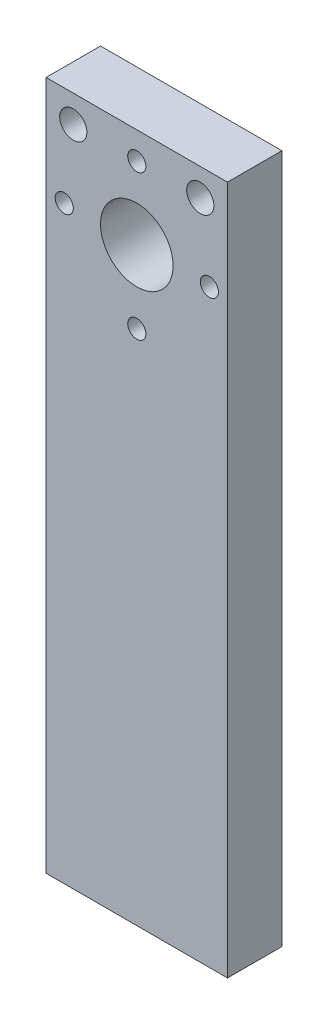
SolidWorks part; units mm, degrees
ref_plane "Plan de face" through (0, 0, 0) normal (0, 0, 1) x (1, 0, 0)
ref_plane "Plan de dessus" through (0, 0, 0) normal (0, 1, 0) x (1, 0, 0)
ref_plane "Plan de droite" through (0, 0, 0) normal (1, 0, 0) x (0, 0, -1)
sketch "Esquisse1" plane through (0, 0, 0) normal (0, 0, 1) x (1, 0, 0)
  line L1 (-10, 38) -> (10, 38)
  line L2 (-10, 38) -> (-10, -38)
  line L3 (-10, -38) -> (10, -38)
  line L4 (10, 38) -> (10, -38)
  dimension "D1" = 76
  dimension "D2" = 20
  dimension "D3" = 10
  dimension "D4" = 38
extrude "Boss.-Extru.1" add sketch "Esquisse1" along normal blind 6
sketch "Esquisse2" plane through (0, 0, 6) normal (0, 0, 1) x (1, 0, 0)
  line L0 (10, 38) -> (-10, 38) construction
  line L1 (45.7904, 0) -> (-37.4617, 0) construction
  line L2 (-19.8072, 35) -> (29.1642, 35) construction
  line L3 (-10, 38) -> (-10, -38) construction
  line L4 (10, -38) -> (10, 38) construction
  circle A0 centre (0, 27) radius 4
  circle A1 centre (0, 27) radius 8 construction
  circle A2 centre (0, 35) radius 1
  circle A3 centre (-8, 27) radius 1
  circle A4 centre (0, 19) radius 1
  circle A5 centre (8, 27) radius 1
  circle A6 centre (-7, 35) radius 1.5
  circle A7 centre (7, 35) radius 1.5
  dimension "D1" = 8
  dimension "D2" = 16
  dimension "D3" = 2
  dimension "D4" = 2
  dimension "D5" = 2
  dimension "D6" = 2
  dimension "D9" = 3
  dimension "D10" = 3
  dimension "D11" = 3
  dimension "D12" = 3
  dimension "D7" = 11
  dimension "D8" = 3
extrude "Enlèv. mat.-Extru.1" cut sketch "Esquisse2" against normal blind 6
equation "\"D3@Esquisse1\"=\"D2@Esquisse1\"/2"
equation "\"D4@Esquisse1\"=\"D1@Esquisse1\"/2"
